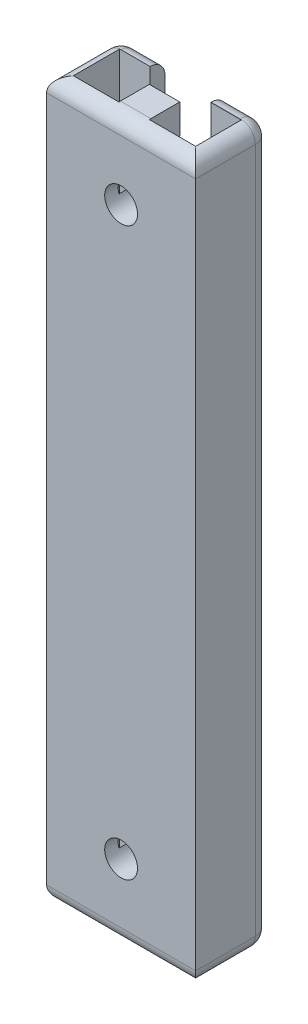
SolidWorks part; units mm, degrees
ref_plane "Front Plane" through (0, 0, 0) normal (0, 0, 1) x (1, 0, 0)
ref_plane "Top Plane" through (0, 0, 0) normal (0, 1, 0) x (1, 0, 0)
ref_plane "Right Plane" through (0, 0, 0) normal (1, 0, 0) x (0, 0, -1)
sketch "Sketch1" plane through (0, 0, 0) normal (0, 1, 0) x (1, 0, 0)
  line L1 (-12.5, -12.5) -> (12.5, -12.5)
  line L2 (-12.5, -12.5) -> (-12.5, 12.5)
  line L3 (-12.5, 12.5) -> (12.5, 12.5)
  line L4 (12.5, -12.5) -> (12.5, 12.5)
  line L5 (-12.5, -12.5) -> (12.5, 12.5) construction
  line L6 (-12.5, 12.5) -> (12.5, -12.5) construction
  point P0 (0, 0)
  dimension "D1" = 25
  dimension "D2" = 25
extrude "Boss-Extrude1" add sketch "Sketch1" along normal blind 120 contours L2 L3 L4 L1
sketch "Sketch2" plane through (0, 120, 0) normal (0, 1, 0) x (1, 0, 0)
  line L0 (0, 10.25) -> (-2.4882, 10.25) construction
  line L1 (-10.25, -10.25) -> (10.25, -10.25)
  line L2 (-10.25, -10.25) -> (-10.25, 10.25)
  line L3 (-10.25, 10.25) -> (10.25, 10.25)
  line L4 (10.25, -10.25) -> (10.25, 10.25)
  line L5 (-10.25, -10.25) -> (10.25, 10.25) construction
  line L6 (-10.25, 10.25) -> (10.25, -10.25) construction
  line L7 (-2.4882, 10.25) -> (-2.4882, 5.15)
  line L8 (-2.4882, 5.15) -> (2.6118, 5.15)
  line L9 (2.6118, 5.15) -> (2.6118, 10.25)
  line L10 (10.25, 2.4882) -> (5.15, 2.4882)
  line L11 (5.15, -2.6118) -> (10.25, -2.6118)
  line L12 (5.15, 2.4882) -> (5.15, -2.6118)
  line L13 (2.4882, -10.25) -> (2.4882, -5.15)
  line L14 (-2.6118, -5.15) -> (-2.6118, -10.25)
  line L15 (2.4882, -5.15) -> (-2.6118, -5.15)
  line L16 (-10.25, -2.4882) -> (-5.15, -2.4882)
  line L17 (-5.15, 2.6118) -> (-10.25, 2.6118)
  line L18 (-5.15, -2.4882) -> (-5.15, 2.6118)
  point P0 (0, 0)
  point P26 (0, 0)
  dimension "D1" = 20.5
  dimension "D2" = 20.5
  dimension "D3" = 5.1
  dimension "D4" = 5.1
  dimension "D5" = 7.7618
  dimension "D6" = 4
extrude "Cut-Extrude1" cut sketch "Sketch2" against normal blind 120 contours L18 L16 L2 L1 L14 L15 L13 L4 L11 L12 L10 L3 L9 L8 L7 L17 region at (0, 120, 0)
sketch "Sketch3" plane through (0, 120, 0) normal (0, 1, 0) x (1, 0, 0)
  line L0 (-12.5, 0) -> (12.5, 0)
  line L1 (-12.5, -12.5) -> (-12.5, 12.5) construction
  line L2 (12.5, -12.5) -> (12.5, 12.5) construction
  line L3 (-12.5, 0) -> (-12.5, 12.5)
  line L4 (-12.5, 12.5) -> (12.5, 12.5)
  line L5 (12.5, 12.5) -> (12.5, 0)
extrude "Cut-Extrude2" cut sketch "Sketch3" against normal blind 120
fillet "Fillet1" radius 2.5 1 edges at (-12.5, 60, 0)
fillet "Fillet2" radius 2.5 1 edges at (12.5, 60, 0)
fillet "Fillet3" radius 2.5 14 edges at (-7.575, 0, 0) (-11.7678, 0, 0.7322) (7.575, 0, 0) (11.7678, 0, 0.7322) (-7.575, 120, 0) (-11.7678, 120, 0.7322) (7.575, 120, 0) (11.7678, 120, 0.7322) (0, 0, 12.5) (-12.5, 0, 7.5) (12.5, 0, 7.5) (-12.5, 120, 7.5) (0, 120, 12.5) (12.5, 120, 7.5)
sketch "Sketch6" plane through (0, 0, 12.5) normal (0, 0, 1) x (1, 0, 0)
  line L0 (0, 117.5) -> (0, 107.5) construction
  line L1 (12.5, 117.5) -> (-12.5, 117.5) construction
  line L2 (0, 2.5) -> (0, 12.5) construction
  line L3 (-12.5, 2.5) -> (12.5, 2.5) construction
  circle A0 centre (0, 107.5) radius 2.75
  circle A1 centre (0, 12.5) radius 2.75
  dimension "D3" = 5.5
  dimension "D4" = 5.5
  dimension "D1" = 10
  dimension "D2" = 10
extrude "Cut-Extrude3" cut sketch "Sketch6" against normal blind 10
sketch "Sketch7" plane through (0, 0, 5.15) normal (0, 0, -1) x (-1, 0, 0)
  line L1 (-5.025, 99.95) -> (5.025, 99.95)
  line L2 (-5.025, 99.95) -> (-5.025, 115.05)
  line L3 (-5.025, 115.05) -> (5.025, 115.05)
  line L4 (5.025, 99.95) -> (5.025, 115.05)
  line L5 (-5.025, 99.95) -> (5.025, 115.05) construction
  line L6 (-5.025, 115.05) -> (5.025, 99.95) construction
  line L7 (-5.025, 4.95) -> (5.025, 4.95)
  line L8 (-5.025, 4.95) -> (-5.025, 20.05)
  line L9 (-5.025, 20.05) -> (5.025, 20.05)
  line L10 (5.025, 4.95) -> (5.025, 20.05)
  line L11 (-5.025, 4.95) -> (5.025, 20.05) construction
  line L12 (-5.025, 20.05) -> (5.025, 4.95) construction
  point P0 (0, 107.5)
  point P6 (0, 12.5)
  dimension "D1" = 15.1
  dimension "D2" = 10.05
  dimension "D3" = 15.1
  dimension "D4" = 10.05
extrude "Cut-Extrude4" cut sketch "Sketch7" against normal blind 2.5
